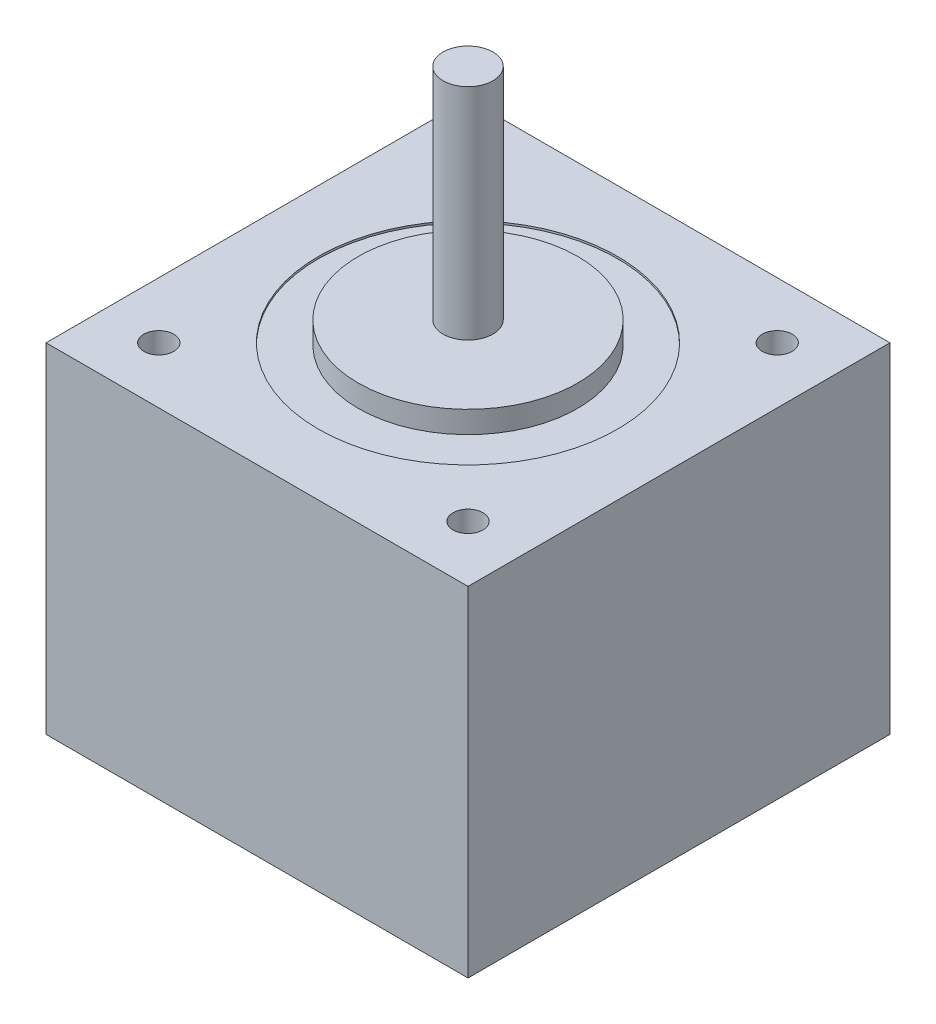
SolidWorks part; units mm, degrees
ref_plane "Front Plane" through (0, 0, 0) normal (0, 0, 1) x (1, 0, 0)
ref_plane "Top Plane" through (0, 0, 0) normal (0, 1, 0) x (1, 0, 0)
ref_plane "Right Plane" through (0, 0, 0) normal (1, 0, 0) x (0, 0, -1)
sketch "Sketch1" plane through (0, 0, 0) normal (0, 1, 0) x (1, 0, 0)
  line L1 (-21.15, 21.15) -> (21.15, 21.15)
  line L2 (-21.15, 21.15) -> (-21.15, -21.15)
  line L3 (-21.15, -21.15) -> (21.15, -21.15)
  line L4 (21.15, 21.15) -> (21.15, -21.15)
  line L5 (-21.15, 21.15) -> (21.15, -21.15) construction
  line L6 (-21.15, -21.15) -> (21.15, 21.15) construction
  point P0 (0, 0)
  dimension "D1" = 42.3
  dimension "D2" = 42.3
extrude "body" add sketch "Sketch1" along normal blind 34
sketch "Sketch2" plane through (0, 34, 0) normal (0, 1, 0) x (1, 0, 0)
  line L1 (-15.5, 15.5) -> (15.5, 15.5) construction
  line L2 (-15.5, 15.5) -> (-15.5, -15.5) construction
  line L3 (-15.5, -15.5) -> (15.5, -15.5) construction
  line L4 (15.5, 15.5) -> (15.5, -15.5) construction
  line L5 (-15.5, 15.5) -> (15.5, -15.5) construction
  line L6 (-15.5, -15.5) -> (15.5, 15.5) construction
  circle A0 centre (-15.5, 15.5) radius 1.5
  circle A1 centre (15.5, 15.5) radius 1.5
  circle A2 centre (15.5, -15.5) radius 1.5
  circle A3 centre (-15.5, -15.5) radius 1.5
  point P0 (0, 0)
  dimension "D3" = 3
  dimension "D4" = 3
  dimension "D5" = 3
  dimension "D6" = 3
  dimension "D1" = 31
  dimension "D2" = 31
extrude "mounting-holes" cut sketch "Sketch2" against normal blind 4
sketch "Sketch3" plane through (0, 34, 0) normal (0, 1, 0) x (1, 0, 0)
  circle A0 centre (0, 0) radius 11
  dimension "D1" = 22
extrude "center-thing" add sketch "Sketch3" along normal blind 2
sketch "Sketch4" plane through (0, 36, 0) normal (0, 1, 0) x (1, 0, 0)
  circle A0 centre (0, 0) radius 2.5
  dimension "D1" = 5
extrude "shaft" add sketch "Sketch4" along normal blind 22
sketch "Sketch5" plane through (0, 34, 0) normal (0, 1, 0) x (1, 0, 0)
  circle A0 centre (0, 0) radius 15
  circle A1 centre (0, 0) radius 11
  dimension "D1" = 30
extrude "large-divot" cut sketch "Sketch5" against normal blind 0.2
